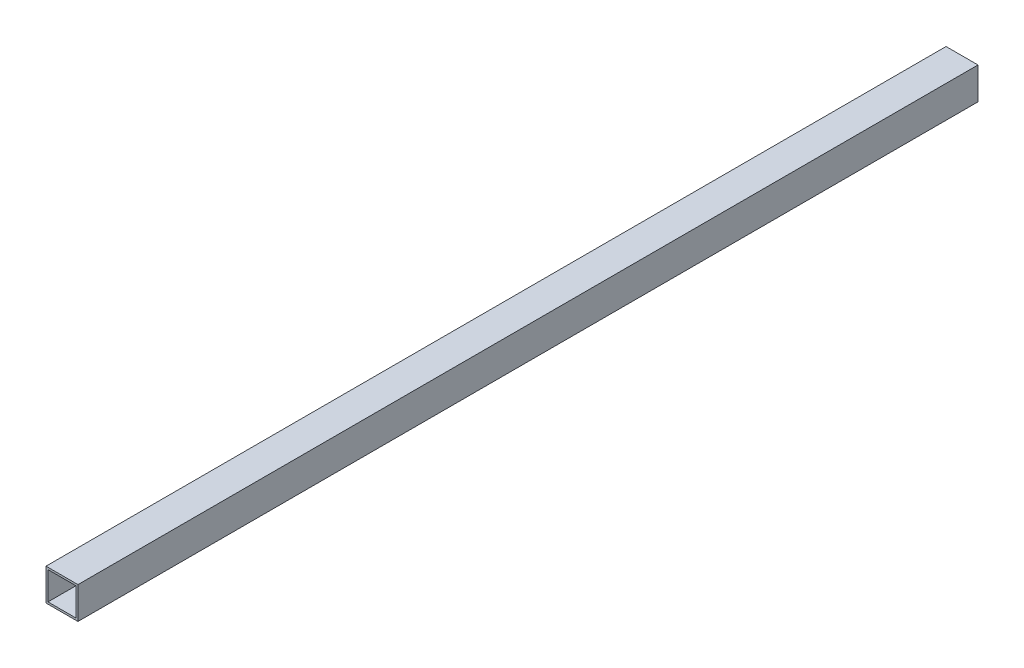
SolidWorks part; units mm, degrees
material "ALUMINUM 6061-T6"
ref_plane "Front Plane" through (0, 0, 0) normal (0, 0, 1) x (1, 0, 0)
ref_plane "Top Plane" through (0, 0, 0) normal (0, 1, 0) x (1, 0, 0)
ref_plane "Right Plane" through (0, 0, 0) normal (1, 0, 0) x (0, 0, -1)
sketch "Sketch1" plane through (0, 0, 0) normal (0, 0, 1) x (1, 0, 0)
  line L0 (11.1125, -11.1125) -> (11.1125, 11.1125)
  line L1 (-12.7, -12.7) -> (12.7, -12.7)
  line L2 (-12.7, -12.7) -> (-12.7, 12.7)
  line L3 (-12.7, 12.7) -> (12.7, 12.7)
  line L4 (12.7, -12.7) -> (12.7, 12.7)
  line L5 (-12.7, -12.7) -> (12.7, 12.7) construction
  line L6 (-12.7, 12.7) -> (12.7, -12.7) construction
  line L7 (-11.1125, 11.1125) -> (11.1125, 11.1125)
  line L8 (-11.1125, -11.1125) -> (-11.1125, 11.1125)
  line L9 (-11.1125, -11.1125) -> (11.1125, -11.1125)
  point P0 (0, 0)
  dimension "D1" = 25.4
  dimension "D2" = 25.4
  dimension "D3" = 1.5875
extrude "Boss-Extrude1" add sketch "Sketch1" along normal mid plane 715.518
